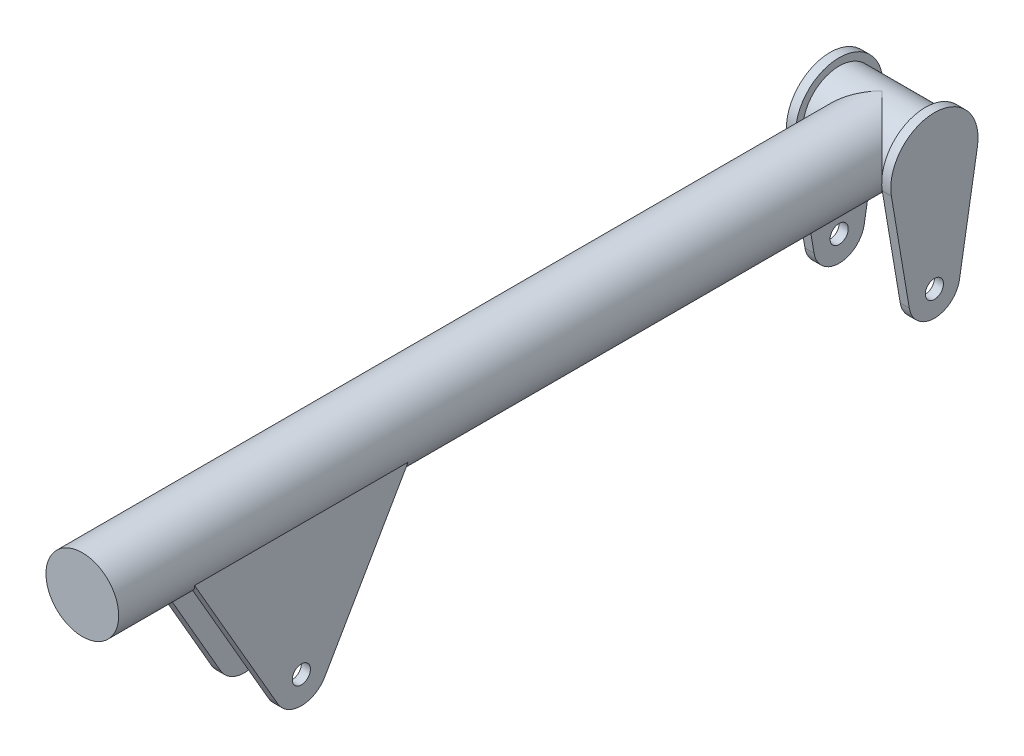
SolidWorks part; units mm, degrees
ref_plane "Front Plane" through (0, 0, 0) normal (1, 0, 0) x (0, 1, 0)
ref_plane "Top Plane" through (0, 0, 0) normal (0, 0, 1) x (0, 1, 0)
ref_plane "Right Plane" through (0, 0, 0) normal (0, 1, 0) x (-1, 0, 0)
sketch "Sketch1" plane through (0, 0, 0) normal (1, 0, 0) x (0, 1, 0)
  line L0 (-39.5817, -8.7657) -> (-2.54, -15.0268)
  line L1 (-39.5817, 8.7657) -> (-2.54, 15.0268)
  line L2 (-55.5625, 206.2086) -> (0, 174.1296)
  line L3 (0, 174.1296) -> (0, 254.7854)
  line L4 (0, 254.7854) -> (-55.5625, 222.7064)
  line L5 (-50.8, 214.4575) -> (0, 214.4575) construction
  arc A0 (-2.54, -15.0268) -> (-2.54, 15.0268) centre (0, 0) ccw
  circle A1 centre (-38.1, 0) radius 3.175
  arc A2 (-39.5817, 8.7657) -> (-39.5817, -8.7657) centre (-38.1, 0) ccw
  circle A3 centre (0, 0) radius 12.7
  arc A4 (-55.5625, 222.7064) -> (-55.5625, 206.2086) centre (-50.8, 214.4575) ccw
  circle A5 centre (-50.8, 214.4575) radius 3.175
  point P10 (214.5347, 49.4206)
  point P17 (-39.1244, 1.7963)
  point P18 (0, 0)
  point P19 (176.3575, 2.0971)
  point P20 (184.1993, 75.7343)
  point P21 (22.0625, 201.3675)
  point P22 (0, 0)
  point P23 (-4.0798, 237.2593)
  point P24 (0, 173.8098)
  dimension "D1" = 30.48
  dimension "D2" = 6.35
  dimension "D3" = 17.78
  dimension "D5" = 25.4
  dimension "D7" = 19.05
  dimension "D4" = 38.1
  dimension "D6" = 214.8332
  dimension "D8" = 50.8
  dimension "D9" = 60
extrude "Boss-Extrude1" add sketch "Sketch1" along normal mid plane 30.099 contours A3
extrude "Boss-Extrude2" add sketch "Sketch1<6>" along normal blind 3.175 from surface contours L1 A2 L0 A0 A3 A1 | A3 region at (0, -20.2102, 0) region at (0, 0, 0) starting at face at (15.0495, 0, -12.7)
sketch "Sketch1<6>" plane through (0, 0, 0) normal (1, 0, 0) x (0, 1, 0) same geometry as "Sketch1"
extrude "Boss-Extrude3" add sketch "Sketch1<8>" along normal blind 3.175 from offset 8.382 separate body contours A5 L3 L4 A4 L2 region at (0, -22.0606, 214.4575)
sketch "Sketch1<8>" plane through (0, 0, 0) normal (1, 0, 0) x (0, 1, 0) same geometry as "Sketch1"
sketch "Sketch2" plane through (0, 0, 0) normal (0, 0, 1) x (-1, 0, 0)
  circle A0 centre (0, 0) radius 12.7
  dimension "D1" = 25.4
extrude "Boss-Extrude4" add sketch "Sketch2" along normal blind 279.4 contours A0
mirror "Mirror1" about plane through (0, 0, 0) normal (1, 0, 0) of bodies 104
